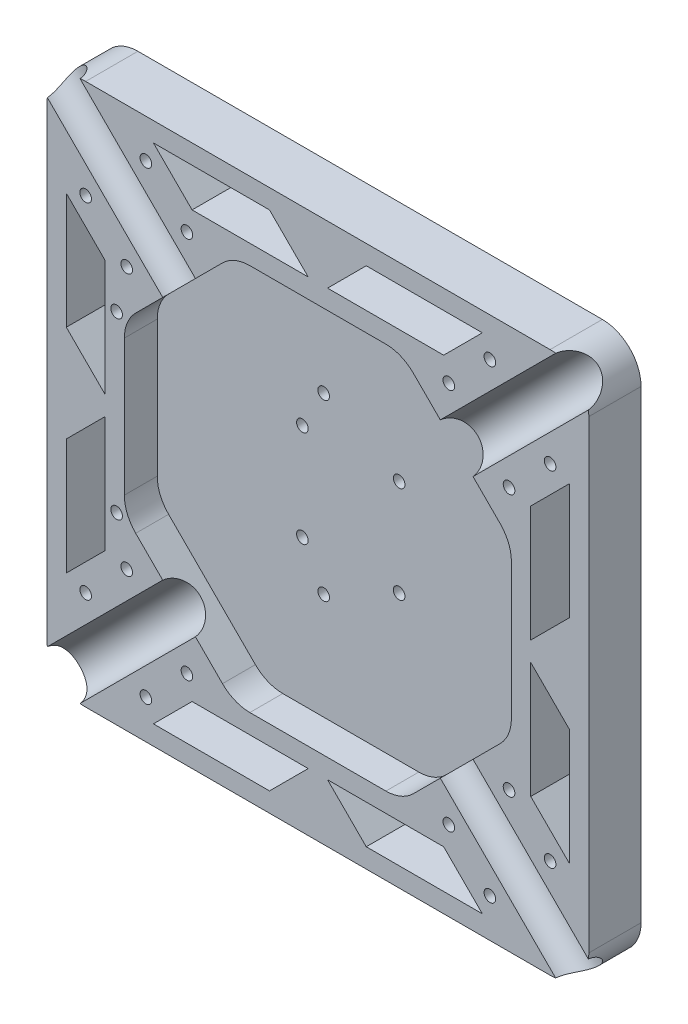
SolidWorks part; units mm, degrees
ref_plane "Plan de face" through (0, 0, 0) normal (0, 0, 1) x (1, 0, 0)
ref_plane "Plan de dessus" through (0, 0, 0) normal (0, 1, 0) x (1, 0, 0)
ref_plane "Plan de droite" through (0, 0, 0) normal (1, 0, 0) x (0, 0, -1)
sketch "Esquisse1" plane through (0, 0, 0) normal (0, 0, 1) x (1, 0, 0)
  line L0 (55, 75.9996) -> (55, -81.4607) construction
  line L1 (-70, 70) -> (70, 70)
  line L2 (-70, 70) -> (-70, -70)
  line L3 (-70, -70) -> (70, -70)
  line L4 (70, 70) -> (70, -70)
  line L9 (65, 75.9996) -> (65, -81.4607) construction
  line L10 (50, 0) -> (70, 0) construction
  line L11 (52.5, 0) -> (65, 12.5) construction
  line L12 (65, 12.5) -> (55, 2.5)
  line L13 (65, -12.5) -> (52.5, 0) construction
  line L14 (65, -12.5) -> (55, -2.5)
  line L15 (65, -12.5) -> (65, -42.5)
  line L16 (65, -42.5) -> (55, -32.5)
  line L17 (55, -32.5) -> (55, -2.5)
  line L18 (65, 12.5) -> (65, 42.5)
  line L19 (65, 42.5) -> (55, 32.5)
  line L20 (55, 32.5) -> (55, 2.5)
  line L21 (12.5, -65) -> (2.5, -55)
  line L22 (-12.5, -65) -> (-2.5, -55)
  line L23 (-12.5, -65) -> (-42.5, -65)
  line L24 (-42.5, -65) -> (-32.5, -55)
  line L25 (-32.5, -55) -> (-2.5, -55)
  line L26 (12.5, -65) -> (42.5, -65)
  line L27 (42.5, -65) -> (32.5, -55)
  line L28 (32.5, -55) -> (2.5, -55)
  line L29 (0, -52.5) -> (12.5, -65) construction
  line L30 (-12.5, -65) -> (0, -52.5) construction
  line L31 (-65, -12.5) -> (-55, -2.5)
  line L32 (-65, 12.5) -> (-55, 2.5)
  line L33 (-65, 12.5) -> (-65, 42.5)
  line L34 (-65, 42.5) -> (-55, 32.5)
  line L35 (-55, 32.5) -> (-55, 2.5)
  line L36 (-65, -12.5) -> (-65, -42.5)
  line L37 (-65, -42.5) -> (-55, -32.5)
  line L38 (-55, -32.5) -> (-55, -2.5)
  line L39 (-52.5, 0) -> (-65, -12.5) construction
  line L40 (-65, 12.5) -> (-52.5, 0) construction
  line L41 (-12.5, 65) -> (-2.5, 55)
  line L42 (12.5, 65) -> (2.5, 55)
  line L43 (12.5, 65) -> (42.5, 65)
  line L44 (42.5, 65) -> (32.5, 55)
  line L45 (32.5, 55) -> (2.5, 55)
  line L46 (-12.5, 65) -> (-42.5, 65)
  line L47 (-42.5, 65) -> (-32.5, 55)
  line L48 (-32.5, 55) -> (-2.5, 55)
  line L49 (0, 52.5) -> (-12.5, 65) construction
  line L50 (12.5, 65) -> (0, 52.5) construction
  dimension "D1" = 140
  dimension "D2" = 140
  dimension "D3" = 70
  dimension "D4" = 70
  dimension "D10" = 5
  dimension "D11" = 2.5
  dimension "D12" = 12.5
  dimension "D13" = 30
  dimension "D14" = 30
  dimension "D15" = 30
  dimension "D16" = 30
  dimension "D17" = 4
extrude "Boss.-Extru.1" add sketch "Esquisse1" along normal blind 13.5
ref_plane "Plan1" through (0, 0, 0) normal (-0.7071, 0.7071, 0) x (-0.7071, -0.7071, 0)
sketch "Esquisse4" plane through (0, 0, 13.5) normal (0, 0, 1) x (1, 0, 0)
  line L0 (-21.7157, 50) -> (-50, 21.7157)
  line L1 (-50, 50) -> (50, 50) construction
  line L2 (-50, 50) -> (-50, -50) construction
  line L3 (-50, -50) -> (50, -50) construction
  line L4 (50, 50) -> (50, -50) construction
  line L5 (-50, -21.7157) -> (-21.7157, -50)
  line L6 (21.7157, -50) -> (50, -21.7157)
  line L7 (21.7157, 50) -> (50, 21.7157)
  line L8 (-50, 21.7157) -> (-50, -21.7157)
  line L9 (-21.7157, -50) -> (21.7157, -50)
  line L10 (50, -21.7157) -> (50, 21.7157)
  line L11 (21.7157, 50) -> (-21.7157, 50)
  dimension "D1" = 100
  dimension "D2" = 100
  dimension "D3" = 50
  dimension "D4" = 50
  dimension "D5" = 20
  dimension "D6" = 20
  dimension "D7" = 20
  dimension "D8" = 20
extrude "Enlèv. mat.-Extru.3" cut sketch "Esquisse4" against normal blind 8.5
sketch "Esquisse2" plane through (0, 0, 0) normal (-0.7071, 0.7071, 0) x (-0.7071, -0.7071, 0)
  line L0 (99.7696, 14) -> (-97.6372, 14) construction
  line L1 (-6, 14) -> (6, 14)
  arc A0 (-6, 14) -> (6, 14) centre (0, 14) ccw
  dimension "D1" = 14
extrude "Enlèv. mat.-Extru.1" cut sketch "Esquisse2" against normal blind 100 and the other way blind 100
ref_axis "Axe1" through (0, 0, -62.842) along (0, 0, 1)
pattern_circular "Répétition circulaire1" count 2 every 90 about axis through (0, 0, -62.842) along (0, 0, 1) of "Enlèv. mat.-Extru.1"
fillet "Congé1" radius 10 12 edges at (-70, 70, 4) (-70, -70, 4) (70, 70, 4) (70, -70, 4) (-21.7157, -50, 9.25) (21.7157, -50, 9.25) (50, -21.7157, 9.25) (50, 21.7157, 9.25) (21.7157, 50, 9.25) (-21.7157, 50, 9.25) (-50, -21.7157, 9.25) (-50, 21.7157, 9.25)
sketch "Esquisse3" plane through (0, 0, 13.5) normal (0, 0, 1) x (1, 0, 0)
  line L0 (-60, -70) -> (60, -70) construction
  line L1 (-70, 60) -> (-70, -60) construction
  line L2 (45.3482, 45.3482) -> (-45.3482, -45.3482) construction
  circle A0 centre (-60, -44.4437) radius 1.5
  circle A1 centre (-44.4437, -60) radius 1.5
  circle A2 centre (-44.4437, 60) radius 1.5
  circle A3 centre (-60, 44.4437) radius 1.5
  circle A4 centre (60, 44.4437) radius 1.5
  circle A5 centre (44.4437, 60) radius 1.5
  circle A6 centre (44.4437, -60) radius 1.5
  circle A7 centre (60, -44.4437) radius 1.5
  dimension "D1" = 3
  dimension "D2" = 3
  dimension "D3" = 10
  dimension "D4" = 10
  dimension "D5" = 11
  dimension "D6" = 11
  dimension "D7" = 4
extrude "Enlèv. mat.-Extru.2" cut sketch "Esquisse3" against normal blind 13.5
sketch "Esquisse5" plane through (0, 0, 5) normal (0, 0, 1) x (1, 0, 0)
  line L0 (-70, 60) -> (-70, -60) construction
  line L1 (60, 70) -> (-60, 70) construction
  line L2 (45.3482, 45.3482) -> (-45.3482, -45.3482) construction
  circle A0 centre (-52, 22.5) radius 1.5
  circle A1 centre (-7, 22.4985) radius 1.5
  circle A2 centre (-52, -22.5) radius 1.5
  circle A3 centre (-7, -22.5015) radius 1.5
  circle A4 centre (-12.5, 12.5) radius 1.5
  circle A5 centre (12.5, 12.5) radius 1.5
  circle A6 centre (12.5, -12.5) radius 1.5
  circle A7 centre (-12.5, -12.5) radius 1.5
  circle A8 centre (33.837, 49.3934) radius 1.5
  circle A9 centre (49.3934, 33.837) radius 1.5
  circle A10 centre (49.3934, -33.837) radius 1.5
  circle A11 centre (33.837, -49.3934) radius 1.5
  circle A12 centre (-33.837, -49.3934) radius 1.5
  circle A13 centre (-49.3934, -33.837) radius 1.5
  circle A14 centre (-49.3934, 33.837) radius 1.5
  circle A15 centre (-33.837, 49.3934) radius 1.5
  circle A16 centre (60, 44.4437) radius 1.5 construction
  circle A17 centre (44.4437, 60) radius 1.5 construction
  dimension "D1" = 3
  dimension "D2" = 3
  dimension "D3" = 3
  dimension "D4" = 3
  dimension "D12" = 3
  dimension "D21" = 3
  dimension "D22" = 3
  dimension "D16" = 15
  dimension "D17" = 11
  dimension "D18" = 15
  dimension "D5" = 45
  dimension "D6" = 45
  dimension "D7" = 45
  dimension "D8" = 45
  dimension "D9" = 52
  dimension "D10" = 22.5
  dimension "D11" = 57.5
  dimension "D13" = 57.5
  dimension "D15" = 11
  dimension "D14" = 4
  dimension "D24" = 4
extrude "Enlèv. mat.-Extru.4" cut sketch "Esquisse5" against normal blind 12.5 and the other way blind 10
